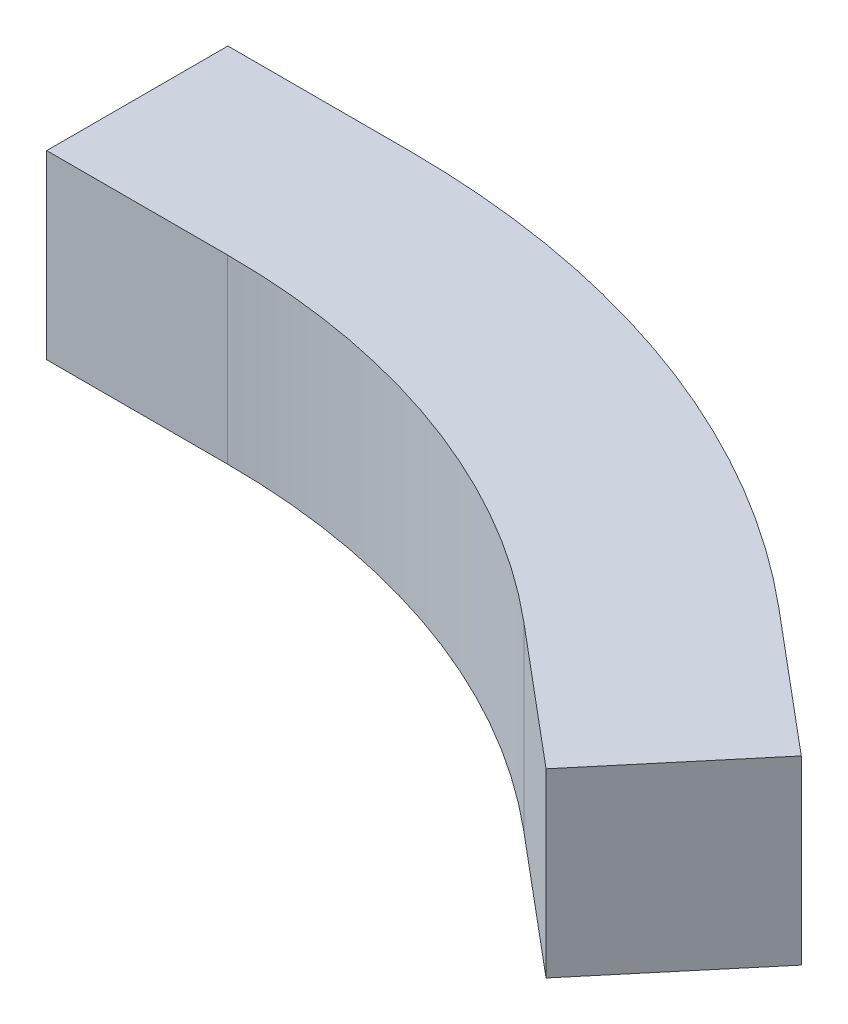
SolidWorks part; units mm, degrees
ref_plane "Front Plane" through (0, 0, 0) normal (0, 0, 1) x (1, 0, 0)
ref_plane "Top Plane" through (0, 0, 0) normal (0, 1, 0) x (1, 0, 0)
ref_plane "Right Plane" through (0, 0, 0) normal (1, 0, 0) x (0, 0, -1)
sketch "Sketch1" plane through (0, 0, 0) normal (0, 1, 0) x (1, 0, 0)
  line L0 (0, 0) -> (0, 75)
  line L1 (0, 0) -> (48.2091, 57.4533)
  line L2 (48.2091, 57.4533) -> (59.6768, 47.8308)
  line L3 (0, 75) -> (-14.97, 75)
  line L4 (0, 75) -> (0, 60)
  line L5 (0, 60) -> (-14.97, 60)
  line L6 (-14.97, 75) -> (-14.97, 60)
  line L7 (59.6768, 47.8308) -> (50.0349, 36.3401)
  line L8 (50.0349, 36.3401) -> (38.5673, 45.9627)
  circle A0 centre (0, 0) radius 75
  circle A1 centre (0, 0) radius 60
  dimension "D1" = 15
  dimension "D2" = 150
  dimension "D3" = 40
  dimension "D4" = 14.97
extrude "Boss-Extrude1" add sketch "Sketch1" along normal blind 15 contours A1 L1 A0 L0 | L7 A0 L1 L8 | A0 L7 L2 | A0 L3 L6 | L0 A0 L6 L5 region at (-7.3554, 0, -67.2565) region at (22.7135, 0, -62.4047) region at (48.8662, 0, -46.7935) region at (-11.2351, 0, -74.548) region at (56.5251, 0, -49.8853)
